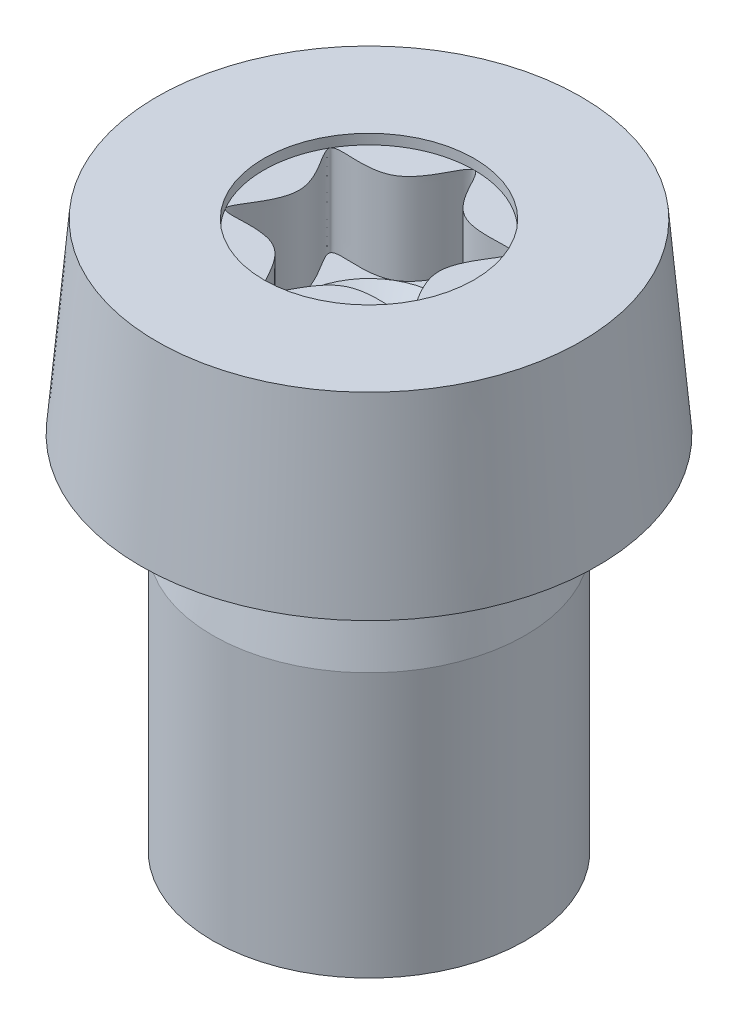
SolidWorks part; units mm, degrees
ref_plane "Front" through (0, 0, 0) normal (0, 0, 1) x (1, 0, 0)
ref_plane "Top" through (0, 0, 0) normal (0, 1, 0) x (1, 0, 0)
ref_plane "Right" through (0, 0, 0) normal (1, 0, 0) x (0, 0, -1)
sketch "Sketch1" plane through (0, 0, 0) normal (0, 0, 1) x (1, 0, 0)
  line L0 (0, 0) -> (0, 5.1006) construction
  line L1 (0, 4.55) -> (1.7644, 4.55)
  line L2 (1.7644, 4.55) -> (1.9, 3)
  line L3 (1.9, 3) -> (1.3, 3)
  line L4 (1.3, 0) -> (1.3, 2.2)
  line L5 (1.3, 0) -> (0, 0)
  line L6 (0, 0) -> (0, 4.55)
  line L7 (1.9, 3) -> (1.9, 2.6) construction
  line L8 (1.3, 2.2) -> (1.14, 3)
  line L9 (1.14, 3) -> (1.3, 3)
  line L10 (1.9, 2.6) -> (1.9, 0.6) construction
  dimension "D1" = 5
  dimension "thread_gap" = 0.8
  dimension "D2" = 0.16
revolve "Body-Revolve" add sketch "Sketch1" angle 360 about L0
cosmetic thread "ThreadCosmetic" [suppressed] parameters "D1"=2, "D2"=2.167
fillet "Fillet1" radius 0.1 1 edges at (0, 3, -1.14)
sketch "Sketch2" plane through (0, 4.55, 0) normal (0, 1, 0) x (-1, 0, 0)
  line L0 (0, -0.9625) -> (0, 0)
  line L1 (0, 0) -> (-0.4375, -0.7578)
  circle A0 centre (0, 0) radius 0.875
  circle A1 centre (0, 0) radius 0.5833
  spline S0 degree 3 poles (0.1887, -0.3269) (0, -1.1491) (-0.1887, -0.3269) (-0.9951, -0.5745) (-0.3774, 0) (-0.9951, 0.5745) (-0.1887, 0.3269) (0, 1.1491) (0.1887, 0.3269) (0.9951, 0.5745) (0.3774, 0) (0.9951, -0.5745) (0.1887, -0.3269) (0, -1.1491) (-0.1887, -0.3269) knots -0.25 -0.166667 -0.083333 0 0.083333 0.166667 0.25 0.333333 0.416667 0.5 0.583333 0.666667 0.75 0.833333 0.916667 1 1.083333 1.166667 1.25 only from (0, -0.875) to (0, -0.875)
  point P5 (0, -0.875)
  point P7 (-0.2917, -0.5052)
  point P10 (-0.7578, -0.4375)
  point P11 (-0.7578, 0.4375)
  point P12 (0, 0.875)
  point P13 (0.7578, 0.4375)
  point P14 (0.7578, -0.4375)
  point P15 (-0.5833, 0)
  point P16 (-0.2917, 0.5052)
  point P17 (0.2917, 0.5052)
  point P18 (0.5833, 0)
  point P19 (0.2917, -0.5052)
  dimension "D1" = 1.1667
  dimension "D2" = 0.9625
  dimension "D3" = 30
extrude "Socket-Cut-Extrude1" cut sketch "Sketch2" against normal blind 0.84 contours S0
sketch "Sketch3" plane through (0, 4.55, 0) normal (0, 1, 0) x (-1, 0, 0)
  circle A0 centre (0, 0) radius 0.875
  dimension "D1" = 1.75
extrude "Socket-Cut-Extrude2" cut sketch "Sketch3" against normal blind 0.084
sketch "Sketch4" plane through (0, 0, 0) normal (0, 0, 1) x (1, 0, 0)
  line L0 (0, 3.71) -> (0.5833, 3.71)
  line L1 (0.761, 3.71) -> (-0.761, 3.71) construction
  line L2 (0.5833, 3.71) -> (0, 3.155)
  line L3 (0, 0) -> (0, 5.1006) construction
  line L4 (0, 3.155) -> (0, 3.71)
  line L5 (0.875, 4.55) -> (-0.875, 4.55) construction
  dimension "D1" = 1.395
  dimension "D2" = 0.5833
revolve "Drill-Cut-Revolve" cut sketch "Sketch4" angle 360 about axis through (0, 0, 0) along (0, 1, 0)
sketch "Sketch5" plane through (0, 0, 0) normal (0, 0, 1) x (1, 0, 0)
  line L0 (1.3, 0) -> (1.0835, 0.125)
  line L1 (1.0835, 0.125) -> (1.3, 0.25)
  line L2 (1.3, 0) -> (1.3, 2.2) construction
  line L3 (1.3, 0.25) -> (1.3, 0)
  line L4 (0, 0) -> (0, 5.1006) construction
  dimension "D1" = 1.0835
revolve "ThreadSchematic" [suppressed] cut sketch "Sketch5" angle 360 about axis through (0, 0, 0) along (0, 1, 0)
pattern_linear "ThdSchPat" [suppressed] count 5 spacing 0.4 along (0, 1, 0) of bodies 105
equation "\"D2@Sketch1\" = 0.2*\"thread_gap@Sketch1\""
equation "\"D1@Sketch2\" = \"socket_dia@Sketch2\" / 1.5"
equation "\"D2@Sketch2\" = \"socket_dia@Sketch2\" / 2 * 1.1"
equation "\"D1@Sketch3\" =\"socket_dia@Sketch2\""
equation "\"D1@Socket-Cut-Extrude2\" = .1 * \"socket_dep@Socket-Cut-Extrude1\""
equation "\"D1@Sketch4\" = 0.9*\"head_ht@Sketch1\""
equation "\"D2@Sketch4\" = \"D1@Sketch2\" / 2"
equation "\"D1@ThreadCosmetic\" = \"thread_length@Sketch1\""
equation "\"D2@ThreadCosmetic\" = \"dia@Sketch1\" - 1.0825 * \"pitch@Sketch1\""
equation "\"D1@Sketch5\" = \"D2@ThreadCosmetic\" / 2"
equation "\"D3@ThdSchPat\" = \"pitch@Sketch1\""
equation "\"D1@ThdSchPat\" = \"thread_length@Sketch1\" / \"pitch@Sketch1\""
